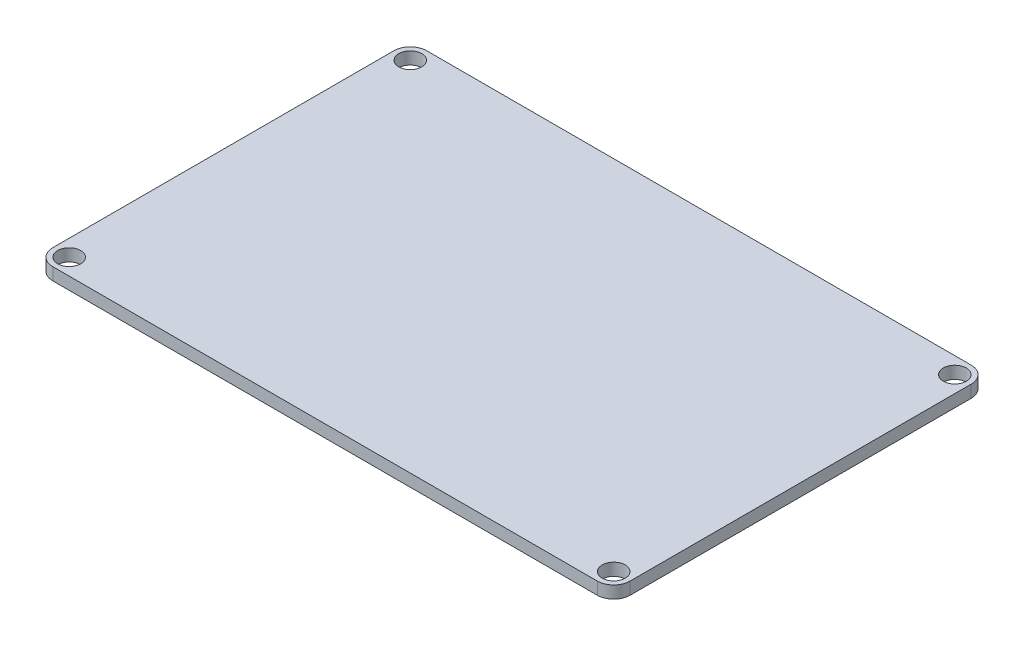
SolidWorks part; units mm, degrees
ref_plane "Front Plane" through (0, 0, 0) normal (0, 0, 1) x (1, 0, 0)
ref_plane "Top Plane" through (0, 0, 0) normal (0, 1, 0) x (1, 0, 0)
ref_plane "Right Plane" through (0, 0, 0) normal (1, 0, 0) x (0, 0, -1)
sketch "Sketch1" plane through (0, 0, 0) normal (0, 1, 0) x (1, 0, 0)
  line L7 (-79.5, -42.5) -> (55, -42.5)
  line L8 (-79.5, -42.5) -> (-79.5, 42.5)
  line L9 (-79.5, 42.5) -> (55, 42.5)
  line L10 (55, -42.5) -> (55, 42.5)
  line L11 (-79.5, -42.5) -> (55, 42.5) construction
  point P0 (0, 0)
  point P6 (-12.25, 0)
  dimension "D1" = 134.5
  dimension "D2" = 42.5
  dimension "D3" = 85
  dimension "D4" = 55
extrude "Boss-Extrude1" add sketch "Sketch1" along normal blind 3
sketch "Sketch2" plane through (0, 0, 0) normal (0, 1, 0) x (1, 0, 0)
  line L0 (55, -42.5) -> (55, 42.5) construction
  line L1 (-82.5, -45.5) -> (58, -45.5)
  line L2 (-82.5, -45.5) -> (-82.5, 45.5)
  line L3 (-82.5, 45.5) -> (58, 45.5)
  line L4 (58, -45.5) -> (58, 45.5)
  line L5 (-82.5, -45.5) -> (58, 45.5) construction
  line L6 (-82.5, 45.5) -> (58, -45.5) construction
  line L7 (-79.5, 42.5) -> (-79.5, -42.5) construction
  line L8 (55, 42.5) -> (-79.5, 42.5) construction
  line L9 (-79.5, -42.5) -> (55, -42.5) construction
  line L11 (-79.5, -42.5) -> (55, -42.5)
  line L12 (-79.5, -42.5) -> (-79.5, 42.5)
  line L13 (-79.5, 42.5) -> (55, 42.5)
  line L14 (55, -42.5) -> (55, 42.5)
  line L15 (-79.5, -42.5) -> (55, 42.5) construction
  line L16 (-79.5, 42.5) -> (55, -42.5) construction
  point P0 (-12.25, 0)
  point P13 (-12.25, 0)
  dimension "D1" = 3
  dimension "D2" = 3
  dimension "D3" = 3
  dimension "D4" = 3
extrude "Boss-Extrude2" add sketch "Sketch2" along normal blind 70
sketch "Sketch3" plane through (0, 3, 0) normal (0, 1, 0) x (1, 0, 0)
  line L1 (-50, -40) -> (50, -40)
  line L2 (-50, -40) -> (-50, 40)
  line L3 (-50, 40) -> (50, 40)
  line L4 (50, -40) -> (50, 40)
  line L5 (-50, -40) -> (50, 40) construction
  line L6 (-50, 40) -> (50, -40) construction
  point P0 (0, 0)
  dimension "D1" = 80
  dimension "D2" = 100
extrude "Boss-Extrude3" add sketch "Sketch3" along normal blind 5 from offset 5 separate body
sketch "Sketch4" plane through (0, 0, -42.5) normal (0, 0, 1) x (1, 0, 0)
  line L5 (55, 3) -> (-79.5, 3) construction
  line L6 (-50, 13) -> (-50, 8) construction
  circle A0 centre (-70.25, 12.25) radius 9.25
  circle A1 centre (-70.25, 30.75) radius 9.25
  line M3 (55, 70) -> (-79.5, 70)
  dimension "D1" = 18.5
  dimension "D2" = 20.25
extrude "Boss-Extrude4" [suppressed] add sketch "Sketch4" along normal blind 33 from surface separate body contours A0 M3 | A1
mirror "Mirror2" [suppressed] about plane through (0, 0, 0) normal (0, 0, 1)
sketch "Sketch5" plane through (0, 3, 0) normal (0, 1, 0) x (1, 0, 0)
  line L1 (-58, -23.5) -> (-61, -23.5)
  line L2 (-58, -23.5) -> (-58, 42.5)
  line L3 (-58, 42.5) -> (-61, 42.5)
  line L4 (-61, -23.5) -> (-61, 42.5)
  line L5 (-58, -23.5) -> (-61, 42.5) construction
  line L6 (-58, 42.5) -> (-61, -23.5) construction
  line L7 (55, 42.5) -> (-79.5, 42.5) construction
  line L8 (-58, -23.5) -> (-58, -26.5)
  line L9 (-58, -26.5) -> (-79.5, -26.5)
  line L10 (-79.5, 42.5) -> (-79.5, -42.5) construction
  line L11 (-79.5, -26.5) -> (-79.5, -23.5)
  line L12 (-79.5, 42.5) -> (-79.5, -42.5) construction
  line L13 (-79.5, -23.5) -> (-61, -23.5)
  point P0 (-59.5, 9.5)
  line M4 (55, 42.5) -> (-79.5, 42.5)
  line M14 (-79.5, 42.5) -> (-79.5, -42.5)
  dimension "D1" = 3
  dimension "D2" = 66
  dimension "D3" = 8
  dimension "D4" = 3
extrude "Boss-Extrude5" add sketch "Sketch5" along normal blind 30 contours L13 L9 L8 L1 M14 | L4 L1 L2 M4 region at (-68.75, 3, 25) region at (-59.5, 3, -9.5)
sketch "Sketch6" plane through (0, 3, 0) normal (0, 1, 0) x (1, 0, 0)
  line L0 (-50, -40) -> (50, -40) construction
  line L1 (-50, 40) -> (-50, -40) construction
  circle A1 centre (-45, -35) radius 3
  circle A2 centre (-45, -35) radius 1
  dimension "D1" = 2
  dimension "D2" = 6
  dimension "D3" = 5
  dimension "D4" = 5
extrude "Boss-Extrude6" add sketch "Sketch6" along normal up to body separate body
sketch "Sketch7" plane through (0, 13, 0) normal (0, 1, 0) x (1, 0, 0)
  line L0 (-50, 40) -> (-50, -40) construction
  line L1 (50, -40) -> (-50, -40)
  line L2 (50, -40) -> (50, 40)
  line L3 (50, 40) -> (-50, 40)
  line L4 (-50, -40) -> (-50, 40)
  line L5 (50, -40) -> (-50, 40) construction
  line L6 (50, 40) -> (-50, -40) construction
  point P0 (0, 0)
  dimension "D1" = 80
extrude "Cut-Extrude2" cut sketch "Sketch7" against normal blind 10 from surface starting at face at (0, 13, 0)
extrude "Boss-Extrude7" add sketch "Sketch6<2>" along normal blind 8
sketch "Sketch6<2>" plane through (0, 3, 0) normal (0, 1, 0) x (1, 0, 0) same geometry as "Sketch6"
mirror "Mirror3" about plane through (0, 0, 0) normal (0, 0, 1) of "Boss-Extrude7"
mirror "Mirror4" about plane through (0, 0, 0) normal (1, 0, 0) of "Boss-Extrude7", "Mirror3"
sketch "Sketch9" plane through (0, 0, 45.5) normal (0, 0, 1) x (1, 0, 0)
  line L1 (-3.15, 67) -> (49.15, 67)
  line L2 (-3.15, 67) -> (-3.15, 14.7)
  line L3 (-3.15, 14.7) -> (49.15, 14.7)
  line L4 (49.15, 67) -> (49.15, 14.7)
  line L5 (-3.15, 67) -> (49.15, 14.7) construction
  line L6 (-3.15, 14.7) -> (49.15, 67) construction
  line L8 (-82.5, 70) -> (58, 70) construction
  line L9 (58, 70) -> (58, 0) construction
  line L10 (-82.5, 70) -> (-82.5, 0) construction
  line L11 (-62.15, 63.1) -> (-32.85, 63.1)
  line L12 (-62.15, 63.1) -> (-62.15, 36.9)
  line L13 (-62.15, 36.9) -> (-32.85, 36.9)
  line L14 (-32.85, 63.1) -> (-32.85, 36.9)
  line L15 (-62.15, 63.1) -> (-32.85, 36.9) construction
  line L16 (-62.15, 36.9) -> (-32.85, 63.1) construction
  line L17 (-47.5, 36.9) -> (-47.5, 0) construction
  line L18 (-82.5, 0) -> (58, 0) construction
  circle A0 centre (23, 40.85) radius 26.15
  circle A1 centre (1.7868, 62.0632) radius 1
  circle A2 centre (44.2132, 62.0632) radius 1
  circle A3 centre (44.2132, 19.6368) radius 1
  circle A4 centre (1.7868, 19.6368) radius 1
  circle A5 centre (-58.75, 21.9) radius 3.4
  circle A6 centre (-40.75, 21.9) radius 7.9
  point P20 (-47.5, 50)
  dimension "D1" = 52.3
  dimension "D3" = 2
  dimension "D8" = 6.8
  dimension "D9" = 15.8
  dimension "D2" = 3
  dimension "D4" = 60
  dimension "D5" = 35
  dimension "D6" = 26.2
  dimension "D7" = 29.3
  dimension "D10" = 35
  dimension "D11" = 50
  dimension "D12" = 15
extrude "Cut-Extrude3" cut sketch "Sketch9" against normal up to surface (3 mm away) contours A0 | A4 | A3 | A2 | A1 | A5 | A6 | L14 L11 L12 L13 region at (23, 40.85, 45.5) region at (-47.5, 50, 45.5) region at (1.7868, 62.0632, 45.5) region at (44.2132, 62.0632, 45.5) region at (44.2132, 19.6368, 45.5) region at (1.7868, 19.6368, 45.5) region at (-58.75, 21.9, 45.5) region at (-40.75, 21.9, 45.5) up to face at (-12.25, 36.5, 42.5)
sketch "Sketch10" plane through (58, 0, 0) normal (1, 0, 0) x (0, 0, -1)
  line L0 (-45.5, 70) -> (45.5, 70) construction
  line L1 (45.5, 70) -> (45.5, 0) construction
  circle A0 centre (15.5, 55) radius 2.95
  circle A1 centre (30.5, 55) radius 5.9
  dimension "D1" = 5.9
  dimension "D2" = 11.8
  dimension "D3" = 15
  dimension "D4" = 15
  dimension "D5" = 15
extrude "Cut-Extrude4" cut sketch "Sketch10" against normal up to surface (3 mm away) up to face at (55, 36.5, 0)
sketch "Sketch11" plane through (0, 70, 0) normal (0, 1, 0) x (1, 0, 0)
  line L0 (50, 37.5) -> (58, 45.5) construction
  line L1 (-79.5, 42.5) -> (-74.5, 42.5)
  line L2 (-79.5, 42.5) -> (-79.5, 37.5)
  line L3 (-79.5, 37.5) -> (-74.5, 37.5)
  line L4 (-74.5, 42.5) -> (-74.5, 37.5)
  line L5 (55, 42.5) -> (50, 42.5)
  line L6 (55, 42.5) -> (55, 37.5)
  line L7 (55, 37.5) -> (50, 37.5)
  line L8 (50, 42.5) -> (50, 37.5)
  line L9 (55, -42.5) -> (50, -42.5)
  line L10 (55, -42.5) -> (55, -37.5)
  line L11 (55, -37.5) -> (50, -37.5)
  line L12 (50, -42.5) -> (50, -37.5)
  line L13 (-79.5, -42.5) -> (-74.5, -42.5)
  line L14 (-79.5, -42.5) -> (-79.5, -37.5)
  line L15 (-79.5, -37.5) -> (-74.5, -37.5)
  line L16 (-74.5, -42.5) -> (-74.5, -37.5)
  line L17 (-79.5, -37.5) -> (-74.5, -42.5)
  line L18 (50, -42.5) -> (55, -37.5)
  line L19 (55, 37.5) -> (50, 42.5)
  line L20 (-79.5, 37.5) -> (-74.5, 42.5)
  line M6 (55, 42.5) -> (55, -42.5)
  line M7 (55, -42.5) -> (-79.5, -42.5)
  line M8 (-79.5, -42.5) -> (-79.5, 42.5)
  line M9 (-79.5, 42.5) -> (55, 42.5)
  dimension "D1" = 5
extrude "Boss-Extrude8" add sketch "Sketch11" against normal blind 7 contours L17 M8 M7 | L20 M8 M9 | L19 L0 M9 | L0 L19 M6 | L18 M7 M6 region at (52.5, 70, -41.6667) region at (54.1667, 70, -40) region at (53.3333, 70, 40.8333) region at (-77.8333, 70, -40.8333) region at (-77.8333, 70, 40.8333)
fillet "Fillet1" radius 4 4 edges at (-82.5, 35, -45.5) (58, 35, -45.5) (58, 35, 45.5) (-82.5, 35, 45.5)
sketch "Sketch13" plane through (0, 70, 0) normal (0, 1, 0) x (1, 0, 0)
  line L0 (-81.3284, 44.3284) -> (-77, 40)
  line L2 (-79.5, 37.5) -> (-74.5, 42.5) construction
  line L4 (-77, 40) -> (-77, -40)
  line L5 (-79.5, -37.5) -> (-74.5, -42.5) construction
  line L6 (-77, -40) -> (-81.3284, -44.3284)
  line L8 (-81.3284, -44.3284) -> (56.8284, -44.3284)
  line L10 (56.8284, -44.3284) -> (52.5, -40)
  line L14 (50, -42.5) -> (55, -37.5) construction
  line L15 (52.5, -40) -> (52.5, 40)
  line L16 (55, 37.5) -> (50, 42.5) construction
  line L17 (52.5, 40) -> (56.8284, 44.3284)
  arc A4 (-78.5, 45.5) -> (-82.5, 41.5) centre (-78.5, 41.5) ccw construction
  arc A5 (-82.5, -41.5) -> (-78.5, -45.5) centre (-78.5, -41.5) ccw construction
  arc A6 (54, -45.5) -> (58, -41.5) centre (54, -41.5) ccw construction
  arc A7 (58, 41.5) -> (54, 45.5) centre (54, 41.5) ccw construction
  circle A8 centre (-79.1642, 42.1642) radius 1
  circle A10 centre (54.6642, 42.1642) radius 1
  circle A11 centre (54.6642, -42.1642) radius 1
  circle A12 centre (-79.1642, -42.1642) radius 1
  dimension "D1" = 2
extrude "Cut-Extrude6" cut sketch "Sketch13" against normal blind 5 contours L17 A10 | L17 A10 | L10 A11 | L6 A12 | L6 A12 | L0 A8 | L0 A8 | A11 region at (-78.8641, 70, -42.4643) region at (54.3641, 70, -42.4643) region at (54.9643, 70, -41.8641) region at (54.9643, 70, 41.8641) region at (-78.8641, 70, 42.4643) region at (-79.4643, 70, 41.8641) region at (-79.4643, 70, -41.8641)
sketch "Sketch14" plane through (0, 70, 0) normal (0, 1, 0) x (1, 0, 0)
  line L0 (-82.5, 41.5) -> (-82.5, -41.5) construction
  line L1 (-78.5, -45.5) -> (54, -45.5)
  line L2 (-82.5, -41.5) -> (-82.5, 41.5)
  line L3 (-78.5, 45.5) -> (54, 45.5)
  line L4 (58, -41.5) -> (58, 41.5)
  line L5 (-82.5, -45.5) -> (58, 45.5) construction
  line L6 (-82.5, 45.5) -> (58, -45.5) construction
  arc A0 (-82.5, -41.5) -> (-78.5, -45.5) centre (-78.5, -41.5) ccw
  arc A1 (54, -45.5) -> (58, -41.5) centre (54, -41.5) ccw
  arc A2 (58, 41.5) -> (54, 45.5) centre (54, 41.5) ccw
  arc A3 (-78.5, 45.5) -> (-82.5, 41.5) centre (-78.5, 41.5) ccw
  circle A4 centre (-78.5, 41.5) radius 2.8
  circle A5 centre (54, 41.5) radius 2.8
  circle A6 centre (54, -41.5) radius 2.8
  circle A7 centre (-78.5, -41.5) radius 2.8
  point P0 (-12.25, 0)
  point P7 (-12.25, 45.5)
  point P8 (-82.5, 0)
  dimension "D4" = 4
  dimension "D5" = 5.6
  dimension "D1" = 140.5
  dimension "D2" = 91
  dimension "D3" = 70.25
extrude "Boss-Extrude9" add sketch "Sketch14" along normal blind 3 separate body
delete or keep bodies "Body-Delete/Keep 1" type delete bodies bodies 118
